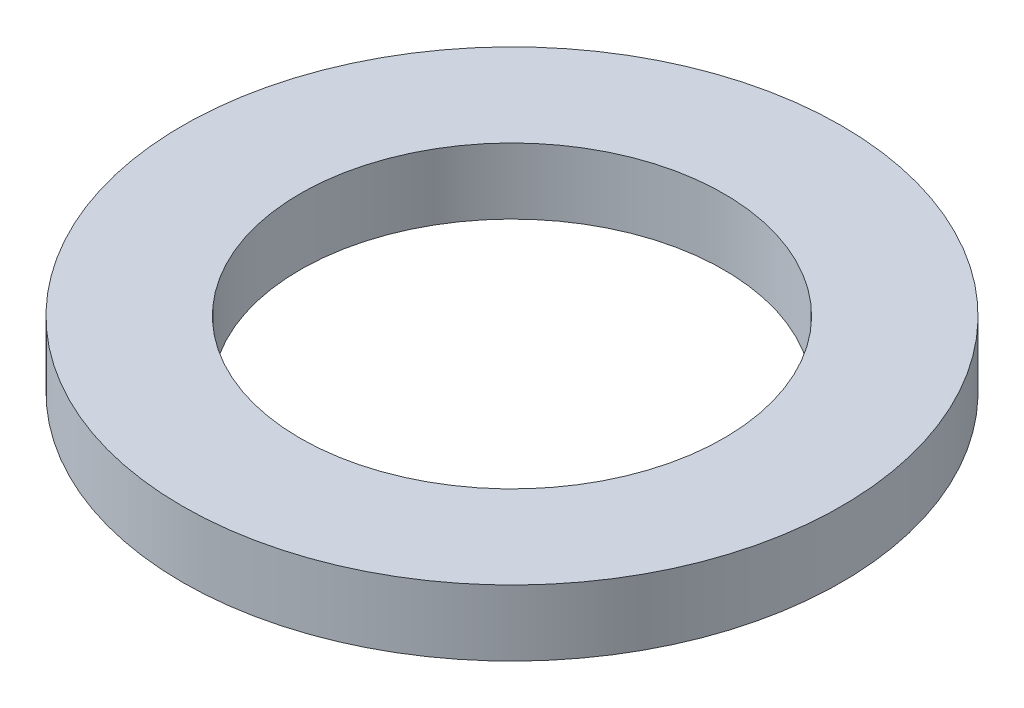
SolidWorks part; units mm, degrees
ref_plane "Front Plane" through (0, 0, 0) normal (0, 0, 1) x (1, 0, 0)
ref_plane "Top Plane" through (0, 0, 0) normal (0, 1, 0) x (1, 0, 0)
ref_plane "Right Plane" through (0, 0, 0) normal (1, 0, 0) x (0, 0, -1)
sketch "Sketch1" plane through (0, 0, 0) normal (0, 1, 0) x (1, 0, 0)
  circle A0 centre (0, 0) radius 70
  dimension "FLANGE_OD" = 140
extrude "Boss-Extrude1" add sketch "Sketch1" along normal blind 14
sketch "Sketch2" plane through (0, 0, 0) normal (0, 1, 0) x (1, 0, 0)
  circle A0 centre (0, 0) radius 45
  dimension "BORE_D" = 90
extrude "Cut-Extrude1" cut sketch "Sketch2" along normal through all
sketch "Sketch3" plane through (0, 14, 0) normal (0, 1, 0) x (1, 0, 0)
  circle A0 centre (0, 0) radius 29.0432 construction
  circle A1 centre (-29.0432, 0) radius 1.6934
  dimension "BOLT_D" = 3.3868
  dimension "BOLT_PCD" = 58.0863
extrude "Cut-Extrude2" cut sketch "Sketch3" against normal blind 13.6826 rebuild error yes
pattern_circular "CirPattern1" count 5 over 360 rebuild error yes
